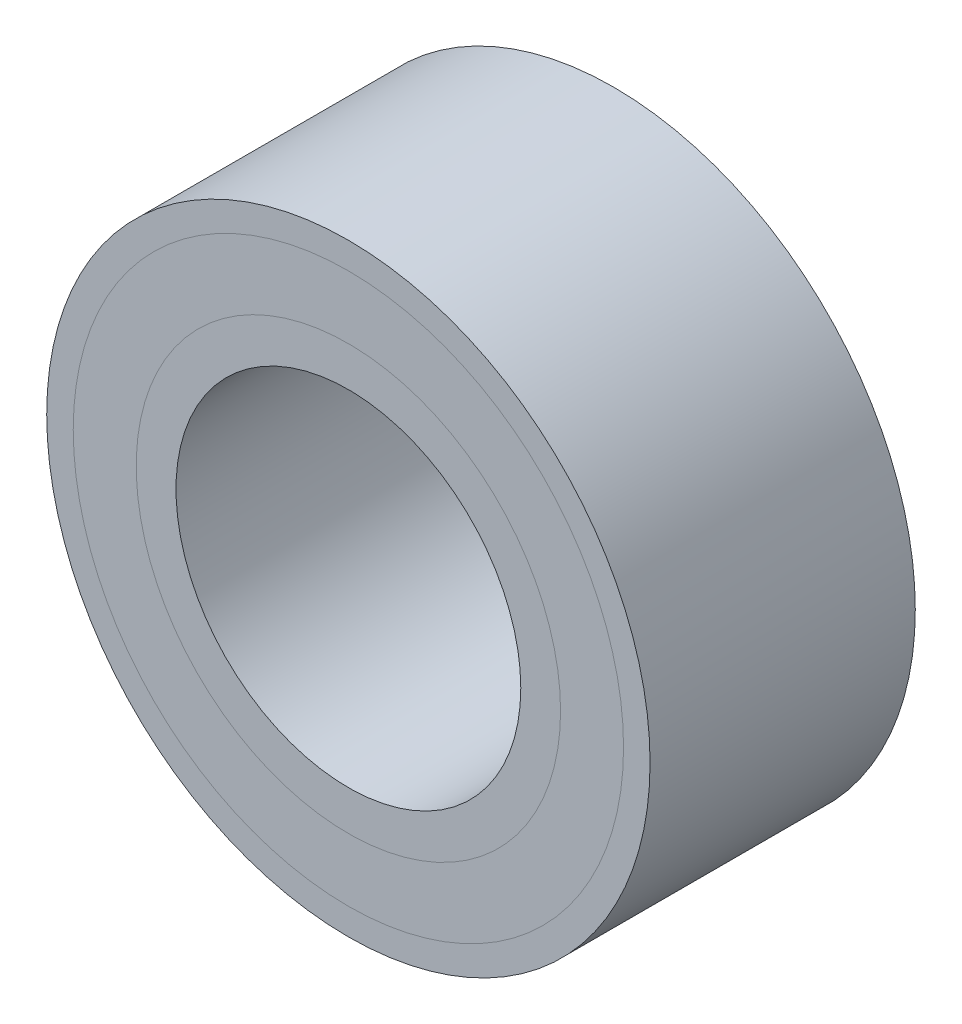
SolidWorks part; units mm, degrees
ref_plane "Front" through (0, 0, 0) normal (0, 0, 1) x (1, 0, 0)
ref_plane "Top" through (0, 0, 0) normal (0, 1, 0) x (1, 0, 0)
ref_plane "Right" through (0, 0, 0) normal (1, 0, 0) x (0, 0, -1)
sketch "Sketch1" plane through (0, 0, 0) normal (0, 0, 1) x (1, 0, 0)
  circle A0 centre (0, 0) radius 45.5
  circle A1 centre (0, 0) radius 26
  circle A2 centre (0, 0) radius 41.5
  circle A3 centre (0, 0) radius 32
  dimension "D1" = 91
  dimension "D2" = 52
  dimension "D3" = 4
  dimension "D4" = 6
extrude "Boss-Extrude1" add sketch "Sketch1" along normal blind 40 contours A0 A2 | A3 A1 region at (-44.2131, 0, 0) region at (-31.0949, 0, 0)
extrude "Boss-Extrude2" add sketch "Sketch1<4>" along normal blind 40 separate body contours A2 A3 region at (-40.3262, 0, 0)
sketch "Sketch1<4>" plane through (0, 0, 0) normal (0, 0, 1) x (1, 0, 0) same geometry as "Sketch1"
